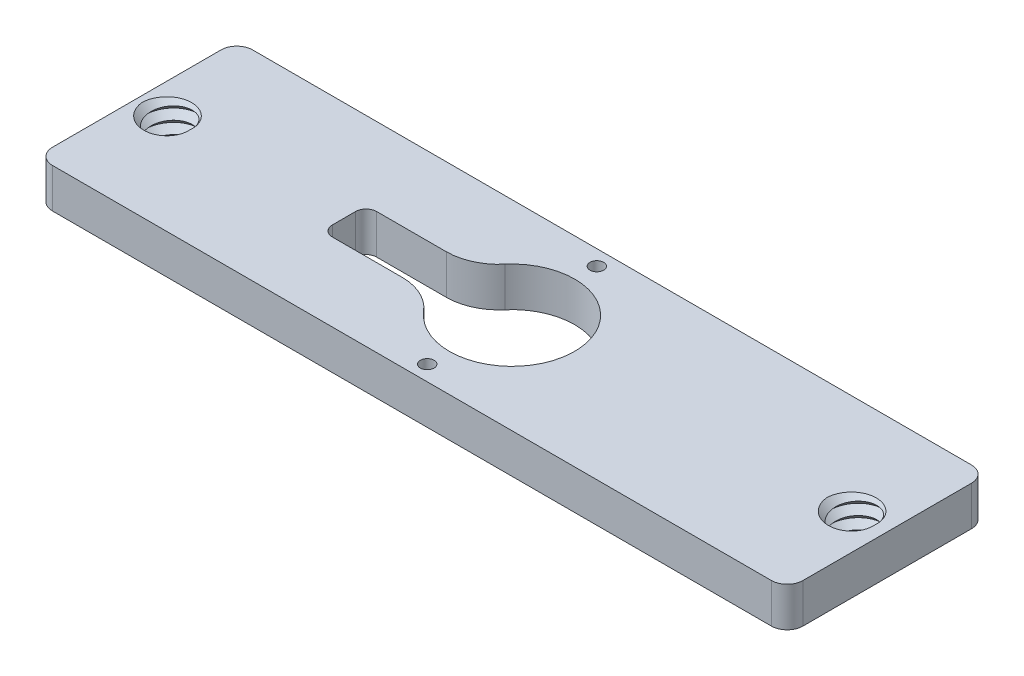
SolidWorks part; units mm, degrees
ref_plane "Front Plane" through (0, 0, 0) normal (0, 0, 1) x (1, 0, 0)
ref_plane "Top Plane" through (0, 0, 0) normal (0, 1, 0) x (1, 0, 0)
ref_plane "Right Plane" through (0, 0, 0) normal (1, 0, 0) x (0, 0, -1)
sketch "Sketch1" plane through (0, 0, 0) normal (0, 1, 0) x (1, 0, 0)
  line L0 (-90.4875, 0) -> (-82.55, 0) construction
  line L1 (-90.4875, -24.13) -> (90.4875, -24.13)
  line L2 (-90.4875, -24.13) -> (-90.4875, 24.13)
  line L3 (-90.4875, 24.13) -> (90.4875, 24.13)
  line L4 (90.4875, -24.13) -> (90.4875, 24.13)
  line L5 (-90.4875, -24.13) -> (90.4875, 24.13) construction
  line L6 (-90.4875, 24.13) -> (90.4875, -24.13) construction
  line L7 (0, 20.447) -> (0, -20.447) construction
  line L8 (90.4875, 0) -> (82.55, 0) construction
  line L9 (-15.113, 0) -> (-40.513, 0) construction
  line L10 (-40.513, 5.334) -> (-40.513, -5.334)
  line L11 (-40.513, 5.334) -> (-14.1404, 5.334)
  line L12 (-40.513, -5.334) -> (-14.1404, -5.334)
  circle A0 centre (0, 0) radius 20.447 construction
  circle A1 centre (0, 20.447) radius 1.651
  circle A2 centre (0, -20.447) radius 1.651
  circle A3 centre (-82.55, 0) radius 5
  circle A4 centre (82.55, 0) radius 5
  circle A5 centre (0, 0) radius 15.113
  point P0 (0, 0)
  point P24 (-40.513, 0)
  dimension "D3" = 40.894
  dimension "D4" = 3.302
  dimension "D6" = 10
  dimension "D7" = 30.226
  dimension "D1" = 180.975
  dimension "D2" = 48.26
  dimension "D5" = 7.9375
  dimension "D8" = 25.4
  dimension "D9" = 10.668
  dimension "D10" = 82.55
extrude "Boss-Extrude1" add sketch "Sketch1" along normal blind 9.525 contours L1 L4 L3 L2 A5 L12 L10 L11 A1 A2 A3 A4 region at (-88.6145, 0, 0)
fillet "Fillet1" radius 2.54 2 edges at (-40.513, 4.7625, -5.334) (-40.513, 4.7625, 5.334)
sketch "Sketch5" plane through (0, 9.525, 0) normal (0, 1, 0) x (1, 0, 0)
  circle A0 centre (-82.55, 0) radius 5 construction
  circle A1 centre (-82.55, 0) radius 5
curve "Helix/Spiral2" pitch 3 height 15 radius 5 left hand yes centre (-82.55, 9.525, 0) axis (0, -1, 0) start towards (0, 0, 1)
sketch "Sketch6" plane through (0, 9.525, 0) normal (0, 1, 0) x (1, 0, 0)
  circle A0 centre (82.55, 0) radius 5 construction
  circle A1 centre (82.55, 0) radius 5
curve "Helix/Spiral3" pitch 3 height 15 radius 5 left hand yes centre (82.55, 9.525, 0) axis (0, -1, 0) start towards (0, 0, 1)
sketch "Sketch7" plane through (0, 0, 0) normal (0, 0, 1) x (1, 0, 0)
  line L0 (-82.55, 9.525) -> (-77.55, 9.525) construction
  line L5 (-77.55, 9.525) -> (-77.55, 12.524)
  line L8 (-77.55, 12.524) -> (-76.0505, 11.0245)
  line L9 (-76.0505, 11.0245) -> (-77.55, 9.525)
  line L10 (-77.55, 11.0245) -> (-76.0505, 11.0245) construction
  spline S0 degree 3 poles (1917.124, -16.8914) (-179.8395, 13.7566) (-98.6601, 11.374) (-78.9229, 9.15) (-77.8102, 8.9625) (-77.4199, 8.775) (-77.8103, 8.5875) (-78.9224, 8.4) (-81.1415, 8.15) (-83.9584, 7.9) (-86.1776, 7.65) (-87.2897, 7.4625) (-87.6802, 7.275) (-87.2897, 7.0875) (-86.1776, 6.9) (-83.9584, 6.65) (-81.1416, 6.4) (-78.9224, 6.15) (-77.8103, 5.9625) (-77.4198, 5.775) (-77.8103, 5.5875) (-78.9224, 5.4) (-81.1416, 5.15) (-83.9584, 4.9) (-86.1776, 4.65) (-87.2897, 4.4625) (-87.6802, 4.275) (-87.2897, 4.0875) (-86.1776, 3.9) (-83.9584, 3.65) (-81.1416, 3.4) (-78.9224, 3.15) (-77.8103, 2.9625) (-77.4198, 2.775) (-77.8103, 2.5875) (-78.9224, 2.4) (-81.1416, 2.15) (-83.9584, 1.9) (-86.1776, 1.65) (-87.2897, 1.4625) (-87.6802, 1.275) (-87.2897, 1.0875) (-86.1776, 0.9) (-83.9584, 0.65) (-81.1416, 0.4) (-78.9224, 0.15) (-77.8103, -0.0375) (-77.4198, -0.225) (-77.8103, -0.4125) (-78.9224, -0.6) (-81.1416, -0.85) (-83.9584, -1.1) (-86.1776, -1.35) (-87.2897, -1.5375) (-87.6802, -1.725) (-87.2897, -1.9125) (-86.1776, -2.1) (-83.9584, -2.35) (-81.1416, -2.6) (-78.9224, -2.85) (-77.8103, -3.0375) (-77.4198, -3.225) (-77.8103, -3.4125) (-78.9224, -3.6) (-81.1416, -3.85) (-83.9585, -4.1) (-86.1776, -4.35) (-87.2897, -4.5375) (-87.6801, -4.725) (-87.2898, -4.9125) (-86.1771, -5.1) (-66.4401, -7.324) (14.7384, -9.7065) (-2082.1793, 20.9407) knots -0.407845 -0.407845 -0.407845 -0.407845 0.0125 0.025 0.0375 0.05 0.0625 0.075 0.0875 0.1125 0.125 0.1375 0.15 0.1625 0.175 0.1875 0.2125 0.225 0.2375 0.25 0.2625 0.275 0.2875 0.3125 0.325 0.3375 0.35 0.3625 0.375 0.3875 0.4125 0.425 0.4375 0.45 0.4625 0.475 0.4875 0.5125 0.525 0.5375 0.55 0.5625 0.575 0.5875 0.6125 0.625 0.6375 0.65 0.6625 0.675 0.6875 0.7125 0.725 0.7375 0.75 0.7625 0.775 0.7875 0.8125 0.825 0.8375 0.85 0.8625 0.875 0.8875 0.9125 0.925 0.9375 0.95 0.9625 0.975 0.9875 1.407842 1.407842 1.407842 1.407842 only from (-82.55, 9.525) to (-82.55, -5.475) construction
  spline S1 degree 3 poles (-82.55, 9.525) (-81.8997, 9.4629) (-80.5849, 9.3373) (-78.9229, 9.15) (-77.8102, 8.9625) (-77.4199, 8.775) (-77.8103, 8.5875) (-78.9224, 8.4) (-81.1415, 8.15) (-83.9584, 7.9) (-86.1776, 7.65) (-87.2897, 7.4625) (-87.6802, 7.275) (-87.2897, 7.0875) (-86.1776, 6.9) (-83.9584, 6.65) (-81.1416, 6.4) (-78.9224, 6.15) (-77.8103, 5.9625) (-77.4198, 5.775) (-77.8103, 5.5875) (-78.9224, 5.4) (-81.1416, 5.15) (-83.9584, 4.9) (-86.1776, 4.65) (-87.2897, 4.4625) (-87.6802, 4.275) (-87.2897, 4.0875) (-86.1776, 3.9) (-83.9584, 3.65) (-81.1416, 3.4) (-78.9224, 3.15) (-77.8103, 2.9625) (-77.4198, 2.775) (-77.8103, 2.5875) (-78.9224, 2.4) (-81.1416, 2.15) (-83.9584, 1.9) (-86.1776, 1.65) (-87.2897, 1.4625) (-87.6802, 1.275) (-87.2897, 1.0875) (-86.1776, 0.9) (-83.9584, 0.65) (-81.1416, 0.4) (-78.9224, 0.15) (-77.8103, -0.0375) (-77.4198, -0.225) (-77.8103, -0.4125) (-78.9224, -0.6) (-81.1416, -0.85) (-83.9584, -1.1) (-86.1776, -1.35) (-87.2897, -1.5375) (-87.6802, -1.725) (-87.2897, -1.9125) (-86.1776, -2.1) (-83.9584, -2.35) (-81.1416, -2.6) (-78.9224, -2.85) (-77.8103, -3.0375) (-77.4198, -3.225) (-77.8103, -3.4125) (-78.9224, -3.6) (-81.1416, -3.85) (-83.9585, -4.1) (-86.1776, -4.35) (-87.2897, -4.5375) (-87.6801, -4.725) (-87.2898, -4.9125) (-86.1771, -5.1) (-84.5151, -5.2873) (-83.2003, -5.4129) (-82.55, -5.475) knots 0 0 0 0 0.0125 0.025 0.0375 0.05 0.0625 0.075 0.0875 0.1125 0.125 0.1375 0.15 0.1625 0.175 0.1875 0.2125 0.225 0.2375 0.25 0.2625 0.275 0.2875 0.3125 0.325 0.3375 0.35 0.3625 0.375 0.3875 0.4125 0.425 0.4375 0.45 0.4625 0.475 0.4875 0.5125 0.525 0.5375 0.55 0.5625 0.575 0.5875 0.6125 0.625 0.6375 0.65 0.6625 0.675 0.6875 0.7125 0.725 0.7375 0.75 0.7625 0.775 0.7875 0.8125 0.825 0.8375 0.85 0.8625 0.875 0.8875 0.9125 0.925 0.9375 0.95 0.9625 0.975 0.9875 1 1 1 1 construction
  dimension "D1" = 2.999
sweep "Cut-Sweep1" cut profiles "Sketch7" path "Helix/Spiral2" align with end faces yes
sketch "Sketch8" plane through (0, 0, 0) normal (0, 0, 1) x (1, 0, 0)
  line L0 (82.55, 9.525) -> (87.55, 9.525) construction
  line L5 (87.55, 9.525) -> (87.55, 12.524)
  line L6 (87.55, 12.524) -> (89.0495, 11.0245)
  line L7 (89.0495, 11.0245) -> (87.55, 9.525)
  line L8 (87.55, 11.0245) -> (89.0495, 11.0245) construction
  spline S0 degree 3 poles (2082.224, -16.8914) (-14.7395, 13.7566) (66.4399, 11.374) (86.1771, 9.15) (87.2898, 8.9625) (87.6801, 8.775) (87.2897, 8.5875) (86.1776, 8.4) (83.9585, 8.15) (81.1416, 7.9) (78.9224, 7.65) (77.8103, 7.4625) (77.4198, 7.275) (77.8103, 7.0875) (78.9224, 6.9) (81.1416, 6.65) (83.9584, 6.4) (86.1776, 6.15) (87.2897, 5.9625) (87.6802, 5.775) (87.2897, 5.5875) (86.1776, 5.4) (83.9584, 5.15) (81.1416, 4.9) (78.9224, 4.65) (77.8103, 4.4625) (77.4198, 4.275) (77.8103, 4.0875) (78.9224, 3.9) (81.1416, 3.65) (83.9584, 3.4) (86.1776, 3.15) (87.2897, 2.9625) (87.6802, 2.775) (87.2897, 2.5875) (86.1776, 2.4) (83.9584, 2.15) (81.1416, 1.9) (78.9224, 1.65) (77.8103, 1.4625) (77.4198, 1.275) (77.8103, 1.0875) (78.9224, 0.9) (81.1416, 0.65) (83.9584, 0.4) (86.1776, 0.15) (87.2897, -0.0375) (87.6802, -0.225) (87.2897, -0.4125) (86.1776, -0.6) (83.9584, -0.85) (81.1416, -1.1) (78.9224, -1.35) (77.8103, -1.5375) (77.4198, -1.725) (77.8103, -1.9125) (78.9224, -2.1) (81.1416, -2.35) (83.9584, -2.6) (86.1776, -2.85) (87.2897, -3.0375) (87.6802, -3.225) (87.2897, -3.4125) (86.1776, -3.6) (83.9584, -3.85) (81.1415, -4.1) (78.9224, -4.35) (77.8103, -4.5375) (77.4199, -4.725) (77.8102, -4.9125) (78.9229, -5.1) (98.6599, -7.324) (179.8384, -9.7065) (-1917.0793, 20.9407) knots -0.407845 -0.407845 -0.407845 -0.407845 0.0125 0.025 0.0375 0.05 0.0625 0.075 0.0875 0.1125 0.125 0.1375 0.15 0.1625 0.175 0.1875 0.2125 0.225 0.2375 0.25 0.2625 0.275 0.2875 0.3125 0.325 0.3375 0.35 0.3625 0.375 0.3875 0.4125 0.425 0.4375 0.45 0.4625 0.475 0.4875 0.5125 0.525 0.5375 0.55 0.5625 0.575 0.5875 0.6125 0.625 0.6375 0.65 0.6625 0.675 0.6875 0.7125 0.725 0.7375 0.75 0.7625 0.775 0.7875 0.8125 0.825 0.8375 0.85 0.8625 0.875 0.8875 0.9125 0.925 0.9375 0.95 0.9625 0.975 0.9875 1.407842 1.407842 1.407842 1.407842 only from (82.55, 9.525) to (82.55, -5.475) construction
  spline S1 degree 3 poles (82.55, 9.525) (83.2003, 9.4629) (84.5151, 9.3373) (86.1771, 9.15) (87.2898, 8.9625) (87.6801, 8.775) (87.2897, 8.5875) (86.1776, 8.4) (83.9585, 8.15) (81.1416, 7.9) (78.9224, 7.65) (77.8103, 7.4625) (77.4198, 7.275) (77.8103, 7.0875) (78.9224, 6.9) (81.1416, 6.65) (83.9584, 6.4) (86.1776, 6.15) (87.2897, 5.9625) (87.6802, 5.775) (87.2897, 5.5875) (86.1776, 5.4) (83.9584, 5.15) (81.1416, 4.9) (78.9224, 4.65) (77.8103, 4.4625) (77.4198, 4.275) (77.8103, 4.0875) (78.9224, 3.9) (81.1416, 3.65) (83.9584, 3.4) (86.1776, 3.15) (87.2897, 2.9625) (87.6802, 2.775) (87.2897, 2.5875) (86.1776, 2.4) (83.9584, 2.15) (81.1416, 1.9) (78.9224, 1.65) (77.8103, 1.4625) (77.4198, 1.275) (77.8103, 1.0875) (78.9224, 0.9) (81.1416, 0.65) (83.9584, 0.4) (86.1776, 0.15) (87.2897, -0.0375) (87.6802, -0.225) (87.2897, -0.4125) (86.1776, -0.6) (83.9584, -0.85) (81.1416, -1.1) (78.9224, -1.35) (77.8103, -1.5375) (77.4198, -1.725) (77.8103, -1.9125) (78.9224, -2.1) (81.1416, -2.35) (83.9584, -2.6) (86.1776, -2.85) (87.2897, -3.0375) (87.6802, -3.225) (87.2897, -3.4125) (86.1776, -3.6) (83.9584, -3.85) (81.1415, -4.1) (78.9224, -4.35) (77.8103, -4.5375) (77.4199, -4.725) (77.8102, -4.9125) (78.9229, -5.1) (80.5849, -5.2873) (81.8997, -5.4129) (82.55, -5.475) knots 0 0 0 0 0.0125 0.025 0.0375 0.05 0.0625 0.075 0.0875 0.1125 0.125 0.1375 0.15 0.1625 0.175 0.1875 0.2125 0.225 0.2375 0.25 0.2625 0.275 0.2875 0.3125 0.325 0.3375 0.35 0.3625 0.375 0.3875 0.4125 0.425 0.4375 0.45 0.4625 0.475 0.4875 0.5125 0.525 0.5375 0.55 0.5625 0.575 0.5875 0.6125 0.625 0.6375 0.65 0.6625 0.675 0.6875 0.7125 0.725 0.7375 0.75 0.7625 0.775 0.7875 0.8125 0.825 0.8375 0.85 0.8625 0.875 0.8875 0.9125 0.925 0.9375 0.95 0.9625 0.975 0.9875 1 1 1 1 construction
  dimension "D1" = 2.999
sweep "Cut-Sweep2" cut profiles "Sketch8" path "Helix/Spiral3" align with end faces yes
fillet "Fillet2" radius 12.7 2 edges at (-14.1404, 4.7625, 5.334) (-14.1404, 4.7625, -5.334)
fillet "Fillet3" radius 3.81 4 edges at (90.4875, 4.7625, -24.13) (90.4875, 4.7625, 24.13) (-90.4875, 4.7625, 24.13) (-90.4875, 4.7625, -24.13)
